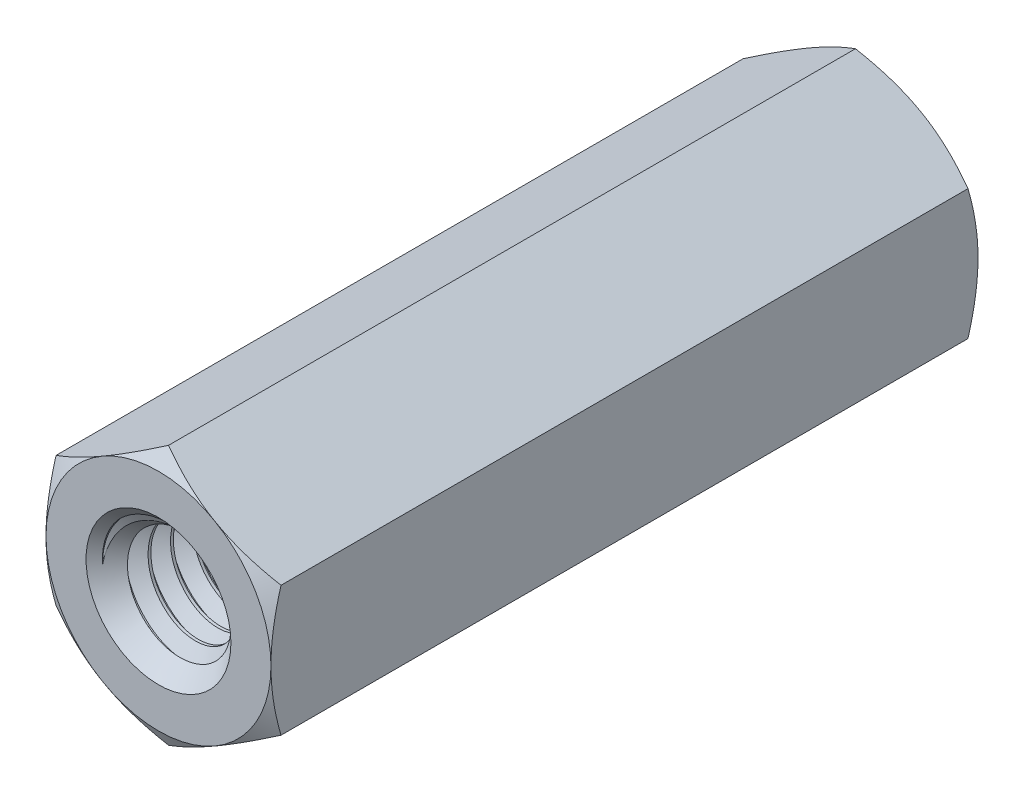
SolidWorks part; units mm, degrees
material "Brass"
ref_plane "Front Plane" through (0, 0, 0) normal (0, 0, 1) x (1, 0, 0)
ref_plane "Top Plane" through (0, 0, 0) normal (0, 1, 0) x (1, 0, 0)
ref_plane "Right Plane" through (0, 0, 0) normal (1, 0, 0) x (0, 0, -1)
sketch "Sketch1" plane through (0, 0, 0) normal (0, 0, 1) x (1, 0, 0)
  line L1 (0, 4.0415) -> (-3.5, 2.0207)
  line L2 (-3.5, 2.0207) -> (-3.5, -2.0207)
  line L3 (-3.5, -2.0207) -> (0, -4.0415)
  line L4 (0, -4.0415) -> (3.5, -2.0207)
  line L5 (3.5, -2.0207) -> (3.5, 2.0207)
  line L6 (3.5, 2.0207) -> (0, 4.0415)
  circle A0 centre (0, 0) radius 3.5 construction
  dimension "Hex" = 7
extrude "Extrude1" add sketch "Sketch1" against normal blind 22
sketch "Sketch2" plane through (0, 0, 0) normal (0, 0, 1) x (1, 0, 0)
  circle A0 centre (0, 0) radius 3.5 construction
  circle A1 centre (0, 0) radius 3.5
extrude "Cut-Extrude1" cut sketch "Sketch2" against normal through all draft 60 flip side to cut
sketch "Sketch3" plane through (0, 0, -22) normal (0, 0, -1) x (-1, 0, 0)
  circle A1 centre (0, 0) radius 3.5
  circle A2 centre (0, 0) radius 3.5
  dimension "D1" = 0
extrude "Cut-Extrude2" cut sketch "Sketch3" against normal through all draft 60 flip side to cut
sketch "Sketch4" plane through (0, 0, 0) normal (0, 0, 1) x (1, 0, 0)
  circle A0 centre (0, 0) radius 2
  dimension "Thread Dia" = 4
extrude "Cut-Extrude3" cut sketch "Sketch4" against normal through all
sketch "Sketch7" plane through (0, 0, 0) normal (0, 0, 1) x (1, 0, 0)
  circle A4 centre (0, 0) radius 2.254
  circle A5 centre (0, 0) radius 2.254
  dimension "D1" = 0.254
sketch "Sketch8" plane through (0, 0, -22) normal (0, 0, -1) x (-1, 0, 0)
  circle A1 centre (0, 0) radius 2.254
  circle A2 centre (0, 0) radius 2.254 construction
sketch "Sketch5" plane through (0, 0, 0) normal (0, 0, 1) x (1, 0, 0)
  circle A0 centre (0, 0) radius 2 construction
  circle A1 centre (0, 0) radius 2
curve "Helix/Spiral1" pitch 0.7 height 22.7 turns 32.4286 parameters "pitch"=0.7
sketch "Sketch9" plane through (0, 0, 0) normal (1, 0, 0) x (0, 0, -1)
  line L0 (-0.35, 2) -> (-0.2625, 2)
  line L1 (-0.2625, 2) -> (0, 1.5453)
  line L2 (-0.35, 2) -> (-0.6125, 1.5453)
  line L3 (-0.6125, 1.5453) -> (0, 1.5453)
  line L4 (-0.3063, 2) -> (-0.3063, 1.5453) construction
  line L5 (-0.4813, 1.7727) -> (-0.1313, 1.7727) construction
  line L7 (0, 1.5453) -> (0, 2) construction
  line L8 (0, 2) -> (0, -2) construction
  dimension "D1" = 0.0875
  dimension "D2" = 0.35
  dimension "D3" = 60
sketch "Sketch12" plane through (0, 0, 0) normal (0, 0, 1) x (1, 0, 0)
  circle A0 centre (0, 0) radius 1.5453
  circle A1 centre (0, 0) radius 2 construction
  circle A2 centre (0, 0) radius 2
extrude "Extrude2" add sketch "Sketch12" against normal up to surface (22 mm away) up to face at (2, 0, -22)
sweep "Cut-Sweep1" cut profiles "Sketch9" path "Helix/Spiral1" align with end faces yes
extrude "Cut-Extrude6" cut sketch "Sketch7" against normal through all draft 45
extrude "Cut-Extrude7" cut sketch "Sketch8" against normal through all draft 45
equation "\"D2@Sketch9\" = \"pitch@Helix/Spiral1\"*.5"
equation "\"D3@Helix/Spiral1\" = \"pitch@Helix/Spiral1\"+\"Height@Extrude1\""
equation "\"D1@Sketch9\" = \"pitch@Helix/Spiral1\"*.125"
